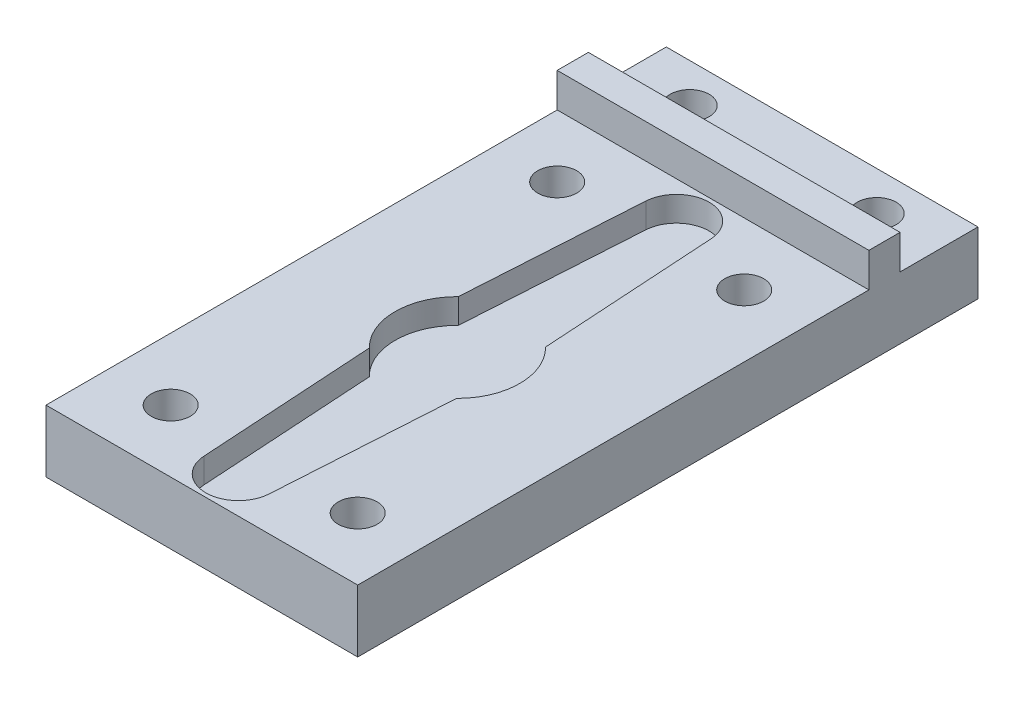
SolidWorks part; units mm, degrees
note: The reader was unsure of these and kept them because the rebuilt part matched: shared geometry of "草图4<3>", "草图5<6>", "草图6<3>".
ref_plane "前视基准面" through (0, 0, 0) normal (0, 0, 1) x (1, 0, 0)
ref_plane "上视基准面" through (0, 0, 0) normal (0, 1, 0) x (1, 0, 0)
ref_plane "右视基准面" through (0, 0, 0) normal (1, 0, 0) x (0, 0, -1)
other "Configuration Table"
sketch "草图1" plane through (0, 0, 0) normal (0, 1, 0) x (1, 0, 0)
  line L1 (0, 0) -> (20, 0)
  line L2 (0, 0) -> (0, -32.8)
  line L3 (0, -32.8) -> (20, -32.8)
  line L4 (20, 0) -> (20, -32.8)
  dimension "D1" = 32.8
  dimension "D2" = 20
extrude "凸台-拉伸1" add sketch "草图1" along normal blind 4
sketch "草图3" plane through (0, 4, 0) normal (0, 1, 0) x (-1, 0, 0)
  line L0 (-7.904, 2.2197) -> (-7.2, 13.5434)
  line L1 (-12.096, 2.2197) -> (-12.8, 13.5434)
  line L2 (-10, 2.35) -> (-10, 30.45) construction
  line L3 (-20, 0) -> (-20, 32.8) construction
  line L4 (0, 0) -> (-20, 0) construction
  line L5 (-12.8, 19.2566) -> (-12.096, 30.5803)
  line L6 (-7.904, 30.5803) -> (-7.2, 19.2566)
  line L7 (-12.8, 13.5434) -> (-7.2, 13.5434) construction
  line L8 (-12.8, 19.2566) -> (-7.2, 19.2566) construction
  circle A0 centre (-10, 16.4) radius 4
  circle A1 centre (-10, 2.35) radius 2.1
  circle A2 centre (-10, 30.45) radius 2.1
  point P13 (-20, 16.4)
  point P18 (-10, 0)
  dimension "D1" = 4.2
  dimension "D2" = 14.05
  dimension "D4" = 5.6
extrude "切除-拉伸1" cut sketch "草图3" against normal blind 1.6 contours A1 L0 A0 L1 | A2 L5 A0 L6
sketch "草图4" plane through (0, 0, 0) normal (0, -1, 0) x (1, 0, 0)
  line L0 (20, 0) -> (20, 32.8) construction
  line L2 (0, 32.8) -> (20, 32.8) construction
  line L3 (0, 0) -> (0, 32.8) construction
  line L4 (0, 0) -> (20, 0) construction
  circle A0 centre (4, 4) radius 1.25
  circle A1 centre (4, 28.8) radius 1.25
  circle A2 centre (16, 4) radius 1.25
  circle A3 centre (16, 28.8) radius 1.25
  circle A5 centre (4, 4) radius 2
  circle A6 centre (4, 28.8) radius 2
  circle A7 centre (16, 28.8) radius 2
  circle A8 centre (16, 4) radius 2
  dimension "D1" = 2.5
  dimension "D2" = 4
  dimension "D3" = 4
  dimension "D4" = 4
  dimension "D5" = 4
  dimension "D6" = 4
extrude "切除-拉伸2" cut sketch "草图4" against normal blind 1.5 contours A6 | A7 | A5 | A8
extrude "切除-拉伸3" cut sketch "草图4<3>" against normal through all contours A1 | A3 | A2 | A0
sketch "草图4<3>" plane through (0, 0, 0) normal (0, -1, 0) x (1, 0, 0) same geometry as "草图4"
sketch "草图5" plane through (0, 0, 0) normal (0, 0, -1) x (-1, 0, 0)
  line L0 (-20, 4) -> (0, 4)
  line L1 (-20, 6.2) -> (0, 6.2)
  line L2 (-20, 6.2) -> (-20, 0)
  line L3 (-20, 0) -> (0, 0)
  line L4 (0, 6.2) -> (0, 0)
  dimension "D1" = 6.2
  dimension "D2" = 20
extrude "凸台-拉伸4" add sketch "草图5" along normal blind 2 contours L4 L3 L2 L1
extrude "凸台-拉伸5" add sketch "草图5<6>" along normal blind 5 from surface at 2 starting at face at (10, 3.1, -2)
sketch "草图5<6>" plane through (0, 0, 0) normal (0, 0, -1) x (-1, 0, 0) same geometry as "草图5"
sketch "草图6" plane through (0, 0, 0) normal (0, -1, 0) x (1, 0, 0)
  line L0 (20, -7) -> (0, -7) construction
  line L1 (0, -7) -> (0, 32.8) construction
  line L2 (20, -7) -> (20, 32.8) construction
  circle A0 centre (4, -4.5) radius 1.25
  circle A1 centre (4, -4.5) radius 2
  circle A2 centre (16, -4.5) radius 1.25
  circle A3 centre (16, -4.5) radius 2
  point P12 (0, 0)
  dimension "D4" = 2.5
  dimension "D5" = 4
  dimension "D1" = 2.5
  dimension "D2" = 4
  dimension "D3" = 4
extrude "切除-拉伸4" cut sketch "草图6" against normal through all contours A0 | A2
extrude "切除-拉伸5" cut sketch "草图6<3>" against normal blind 1.5 contours A1 | A3
sketch "草图6<3>" plane through (0, 0, 0) normal (0, -1, 0) x (1, 0, 0) same geometry as "草图6"
